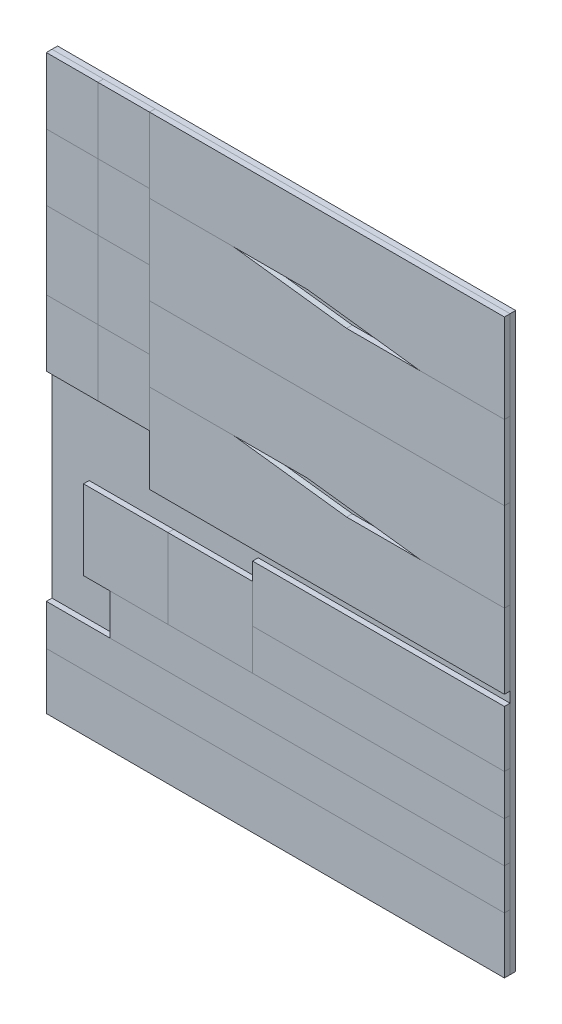
SolidWorks part; units mm, degrees
ref_plane "Front Plane" through (0, 0, 0) normal (0, 0, 1) x (1, 0, 0)
ref_plane "Top Plane" through (0, 0, 0) normal (0, 1, 0) x (1, 0, 0)
ref_plane "Right Plane" through (0, 0, 0) normal (1, 0, 0) x (0, 0, -1)
sketch "Sketch1" plane through (0, 0, 0) normal (0, 0, 1) x (1, 0, 0)
  line L0 (183, 1016) -> (183, 883.5)
  line L1 (0, 0) -> (813, 0)
  line L2 (0, 0) -> (0, 1016)
  line L3 (0, 1016) -> (813, 1016)
  line L4 (813, 0) -> (813, 1016)
  line L9 (183, 883.5) -> (463, 883.5)
  line L10 (463, 883.5) -> (663, 858.5)
  line L11 (663, 858.5) -> (813, 858.5)
  line L12 (813, 858.5) -> (813, 1016)
  line L13 (813, 1016) -> (183, 1016)
  line L21 (113, 244.92) -> (813, 244.92)
  line L22 (113, 244.92) -> (113, 172.46)
  line L23 (113, 172.46) -> (813, 172.46)
  line L24 (813, 244.92) -> (813, 172.46)
  line L25 (0, 100) -> (813, 100)
  line L26 (0, 100) -> (0, 0)
  line L27 (0, 0) -> (813, 0)
  line L28 (813, 100) -> (813, 0)
  line L29 (183, 883.5) -> (183, 726)
  line L30 (183, 726) -> (813, 726)
  line L31 (813, 726) -> (813, 858.5)
  line L33 (333, 883.5) -> (533, 858.5)
  line L34 (533, 858.5) -> (663, 858.5)
  line L35 (813, 726) -> (183, 726)
  line L36 (183, 726) -> (183, 593.5)
  line L37 (183, 593.5) -> (463, 593.5)
  line L38 (463, 593.5) -> (663, 568.5)
  line L39 (663, 568.5) -> (813, 568.5)
  line L40 (813, 568.5) -> (813, 726)
  line L41 (183, 593.5) -> (183, 436)
  line L42 (183, 436) -> (813, 436)
  line L43 (333, 593.5) -> (533, 568.5)
  line L44 (533, 568.5) -> (663, 568.5)
  line L45 (91.5, 643.64) -> (183, 643.64)
  line L46 (0, 643.64) -> (91.5, 643.64)
  line L47 (0, 643.64) -> (0, 526.2)
  line L48 (0, 526.2) -> (91.5, 526.2)
  line L49 (91.5, 643.64) -> (91.5, 526.2)
  line L50 (91.5, 781.08) -> (183, 781.08)
  line L51 (91.5, 781.08) -> (91.5, 643.64)
  line L52 (91.5, 643.64) -> (183, 643.64)
  line L53 (183, 781.08) -> (183, 643.64)
  line L54 (91.5, 898.54) -> (183, 898.54)
  line L55 (91.5, 898.54) -> (91.5, 1016)
  line L56 (91.5, 1016) -> (183, 1016)
  line L57 (183, 898.54) -> (183, 1016)
  line L58 (91.5, 898.54) -> (0, 898.54)
  line L59 (91.5, 898.54) -> (91.5, 1016)
  line L60 (91.5, 1016) -> (0, 1016)
  line L61 (0, 898.54) -> (0, 1016)
  line L62 (366, 417.38) -> (813, 417.38)
  line L63 (366, 417.38) -> (366, 317.38)
  line L64 (366, 317.38) -> (813, 317.38)
  line L65 (813, 417.38) -> (813, 317.38)
  line L66 (0, 172.46) -> (813, 172.46)
  line L67 (0, 172.46) -> (0, 100)
  line L68 (0, 100) -> (813, 100)
  line L69 (813, 172.46) -> (813, 100)
  line L70 (366, 317.38) -> (813, 317.38)
  line L71 (366, 317.38) -> (366, 244.92)
  line L72 (366, 244.92) -> (813, 244.92)
  line L73 (813, 317.38) -> (813, 244.92)
  line L74 (91.5, 643.64) -> (91.5, 526.2)
  line L75 (91.5, 526.2) -> (183, 526.2)
  line L76 (183, 643.64) -> (183, 526.2)
  line L77 (0, 781.08) -> (91.5, 781.08)
  line L78 (0, 781.08) -> (0, 643.64)
  line L79 (0, 643.64) -> (91.5, 643.64)
  line L80 (91.5, 781.08) -> (91.5, 643.64)
  line L81 (91.5, 781.08) -> (183, 781.08)
  line L82 (91.5, 781.08) -> (91.5, 898.54)
  line L83 (91.5, 898.54) -> (183, 898.54)
  line L84 (183, 781.08) -> (183, 898.54)
  line L85 (91.5, 781.08) -> (0, 781.08)
  line L86 (91.5, 781.08) -> (91.5, 898.54)
  line L87 (91.5, 898.54) -> (0, 898.54)
  line L88 (0, 781.08) -> (0, 898.54)
  line L90 (216, 244.92) -> (366, 244.92)
  line L91 (216, 244.92) -> (216, 386.11)
  line L92 (216, 386.11) -> (366, 386.11)
  line L93 (366, 244.92) -> (366, 386.11)
  line L94 (66, 244.92) -> (216, 244.92)
  line L95 (66, 244.92) -> (66, 386.11)
  line L96 (66, 386.11) -> (216, 386.11)
  line L97 (216, 244.92) -> (216, 386.11)
  dimension "D1" = 813
  dimension "D2" = 1016
  dimension "D3" = 157.5
  dimension "D4" = 132.5
  dimension "D5" = 630
  dimension "D6" = 280
  dimension "D7" = 200
  dimension "D8" = 72.46
  dimension "D9" = 700
  dimension "D10" = 100
  dimension "D12" = 157.5
  dimension "D13" = 280
  dimension "D14" = 200
  dimension "D15" = 2
  dimension "D16" = 132.5
  dimension "D17" = 150
  dimension "D18" = 117.44
  dimension "D19" = 141.19
  dimension "D20" = 150
  dimension "D21" = 91.5
  dimension "D22" = 117.46
  dimension "D23" = 100
  dimension "D24" = 447
  dimension "D25" = 72.46
  dimension "D26" = 72.46
  dimension "D28" = 447
  dimension "D31" = 91.5
  dimension "D32" = 137.44
  dimension "D34" = 117.46
  dimension "D35" = 0
extrude "Boss-Extrude2" add sketch "Sketch1" along normal blind 10 contours L10 L11 L4 L3 L0 L9 | L38 L39 L4 L30 L36 L37 | L77 L82 L58 L2 | L49 L46 L2 L48 | L63 L64 L4 L62 | L96 L95 L94 L21 L91 | L66 L2 L25 L4 L23 region at (510.7705, 944.3806, 0) region at (45.75, 839.81, 0) region at (510.7705, 654.3806, 0) region at (45.75, 584.92, 0) region at (589.5, 367.38, 0) region at (406.5, 136.23, 0) region at (141, 315.515, 0)
extrude "Boss-Extrude3" add sketch "Sketch1<4>" along normal blind 10 separate body contours L34 L33 L9 L29 L30 L4 L11 | L58 L55 L3 L2 | L77 L2 L46 L51 | L44 L43 L37 L41 L42 L4 L39 | L92 L91 L21 L71 L63 | L25 L2 L1 L4 region at (45.75, 957.27, 0) region at (485.2295, 797.6194, 0) region at (45.75, 712.36, 0) region at (485.2295, 507.6194, 0) region at (406.5, 50, 0) region at (291, 315.515, 0)
sketch "Sketch1<4>" plane through (0, 0, 0) normal (0, 0, 1) x (1, 0, 0) same geometry as "Sketch1"
extrude "Boss-Extrude4" add sketch "Sketch1<5>" along normal blind 10 separate body contours L64 L71 L21 L4 | L45 L76 L75 L74 | L81 L84 L83 L82 region at (589.5, 281.15, 0)
sketch "Sketch1<5>" plane through (0, 0, 0) normal (0, 0, 1) x (1, 0, 0) same geometry as "Sketch1"
extrude "Boss-Extrude5" add sketch "Sketch1<6>" along normal blind 10 separate body contours L22 L23 L4 L21 | L51 L50 L53 L52 | L55 L54 L57 L56 region at (463, 208.69, 0)
sketch "Sketch1<6>" plane through (0, 0, 0) normal (0, 0, 1) x (1, 0, 0) same geometry as "Sketch1"
extrude "Boss-Extrude6" add sketch "Sketch1<8>" against normal blind 10 separate body contours L10 L11 L4 L3 L0 L9 | L34 L33 L9 L29 L30 L4 L11 | L38 L39 L4 L30 L36 L37 | L44 L43 L37 L41 L42 L4 L39 | L33 L34 L10 L9 | L43 L44 L38 L37 | L95 L96 L92 L63 L62 L4 L42 L41 L36 L29 L0 L3 L57 L84 L53 L76 L75 L48 L2 L66 L22 L94 | L50 L84 L54 L82 | L54 L57 L3 L55 | L58 L55 L3 L2 | L77 L82 L58 L2 | L77 L2 L46 L51 | L53 L50 L51 L45 | L76 L45 L49 L75 | L49 L46 L2 L48 | L63 L64 L4 L62 | L92 L91 L21 L71 L63 | L96 L95 L94 L21 L91 | L64 L71 L21 L4 | L22 L23 L4 L21 | L66 L2 L25 L4 L23 | L25 L2 L1 L4 region at (510.7705, 944.3806, 0) region at (137.25, 957.27, 0) region at (137.25, 839.81, 0) region at (45.75, 957.27, 0) region at (485.2295, 797.6194, 0) region at (45.75, 839.81, 0) region at (498, 871, 0) region at (137.25, 712.36, 0) region at (45.75, 712.36, 0) region at (510.7705, 654.3806, 0) region at (45.75, 584.92, 0) region at (137.25, 584.92, 0) region at (485.2295, 507.6194, 0) region at (173.7493, 390.2464, 0) region at (498, 581, 0) region at (589.5, 367.38, 0) region at (406.5, 136.23, 0) region at (589.5, 281.15, 0) region at (406.5, 50, 0) region at (463, 208.69, 0) region at (291, 315.515, 0) region at (141, 315.515, 0)
sketch "Sketch1<8>" plane through (0, 0, 0) normal (0, 0, 1) x (1, 0, 0) same geometry as "Sketch1"
